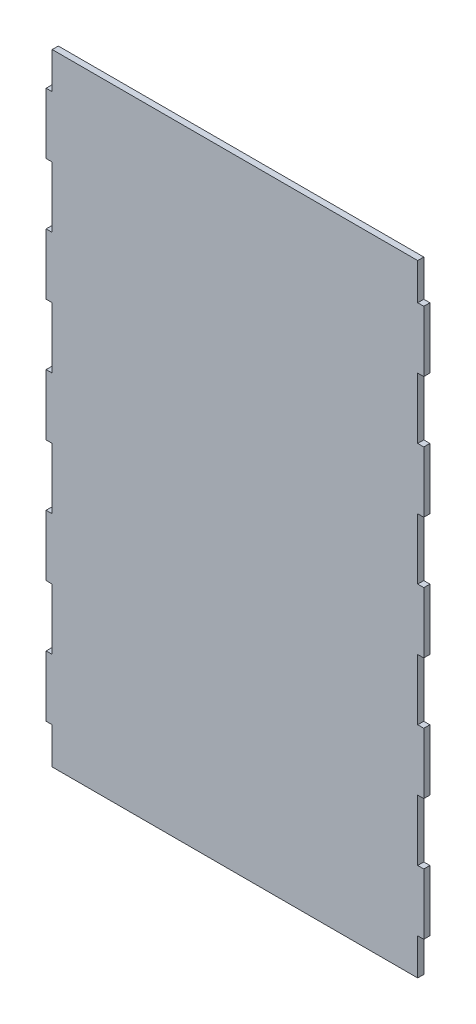
SolidWorks part; units mm, degrees
material "ﾁｰｸ材"
ref_plane "正面" through (0, 0, 0) normal (0, 0, 1) x (1, 0, 0)
ref_plane "平面" through (0, 0, 0) normal (0, 1, 0) x (1, 0, 0)
ref_plane "右側面" through (0, 0, 0) normal (1, 0, 0) x (0, 0, -1)
sketch "ｽｹｯﾁ1" plane through (0, 0, 0) normal (0, 0, 1) x (1, 0, 0)
  line L1 (155, 255) -> (-155, 255)
  line L2 (155, 255) -> (155, -255)
  line L3 (155, -255) -> (-155, -255)
  line L4 (-155, 255) -> (-155, -255)
  line L5 (155, 255) -> (-155, -255) construction
  line L6 (155, -255) -> (-155, 255) construction
  point P0 (0, 0)
  dimension "D1" = 310
  dimension "D2" = 510
extrude "ﾎﾞｽ - 押し出し1" add sketch "ｽｹｯﾁ1" along normal blind 5
sketch "ｽｹｯﾁ2" plane through (0, 0, 5) normal (0, 0, 1) x (1, 0, 0)
  line L0 (155, -255) -> (155, 255) construction
  line L1 (155, 25) -> (150, 25)
  line L2 (155, 25) -> (155, 75)
  line L3 (155, 75) -> (150, 75)
  line L4 (150, 25) -> (150, 75)
  line L9 (155, -75) -> (150, -75)
  line L10 (155, -75) -> (155, -25)
  line L11 (155, -25) -> (150, -25)
  line L12 (150, -75) -> (150, -25)
  line L13 (155, 125) -> (150, 125)
  line L14 (155, 125) -> (155, 175)
  line L15 (155, 175) -> (150, 175)
  line L16 (150, 125) -> (150, 175)
  line L17 (155, -175) -> (150, -175)
  line L18 (155, -175) -> (155, -125)
  line L19 (155, -125) -> (150, -125)
  line L20 (150, -175) -> (150, -125)
  line L21 (155, 225) -> (150, 225)
  line L22 (155, 225) -> (155, 275)
  line L23 (155, 275) -> (150, 275)
  line L24 (150, 225) -> (150, 275)
  line L25 (155, -275) -> (150, -275)
  line L26 (155, -275) -> (155, -225)
  line L27 (155, -225) -> (150, -225)
  line L28 (150, -275) -> (150, -225)
  line L29 (-150, 25) -> (-155, 25)
  line L30 (-150, 25) -> (-150, 75)
  line L31 (-150, 75) -> (-155, 75)
  line L32 (-155, 25) -> (-155, 75)
  line L33 (-150, -75) -> (-155, -75)
  line L34 (-150, -75) -> (-150, -25)
  line L35 (-150, -25) -> (-155, -25)
  line L36 (-155, -75) -> (-155, -25)
  line L37 (-150, 125) -> (-155, 125)
  line L38 (-150, 125) -> (-150, 175)
  line L39 (-150, 175) -> (-155, 175)
  line L40 (-155, 125) -> (-155, 175)
  line L41 (-150, -175) -> (-155, -175)
  line L42 (-150, -175) -> (-150, -125)
  line L43 (-150, -125) -> (-155, -125)
  line L44 (-155, -175) -> (-155, -125)
  line L45 (-150, 225) -> (-155, 225)
  line L46 (-150, 225) -> (-150, 275)
  line L47 (-150, 275) -> (-155, 275)
  line L48 (-155, 225) -> (-155, 275)
  line L49 (-150, -275) -> (-155, -275)
  line L50 (-150, -275) -> (-150, -225)
  line L51 (-150, -225) -> (-155, -225)
  line L52 (-155, -275) -> (-155, -225)
  line L53 (-155, 255) -> (-155, -255) construction
  point P53 (-152.5, 25)
  dimension "D1" = 5
  dimension "D2" = 50
  dimension "D3" = 25
  dimension "D4" = 50
  dimension "D5" = 50
  dimension "D6" = 50
  dimension "D7" = 50
  dimension "D8" = 50
  dimension "D9" = 5
  dimension "D10" = 50
  dimension "D11" = 50
  dimension "D12" = 50
  dimension "D13" = 50
  dimension "D14" = 50
  dimension "D15" = 50
  dimension "D16" = 25
extrude "ｶｯﾄ - 押し出し1" cut sketch "ｽｹｯﾁ2" against normal blind 5
